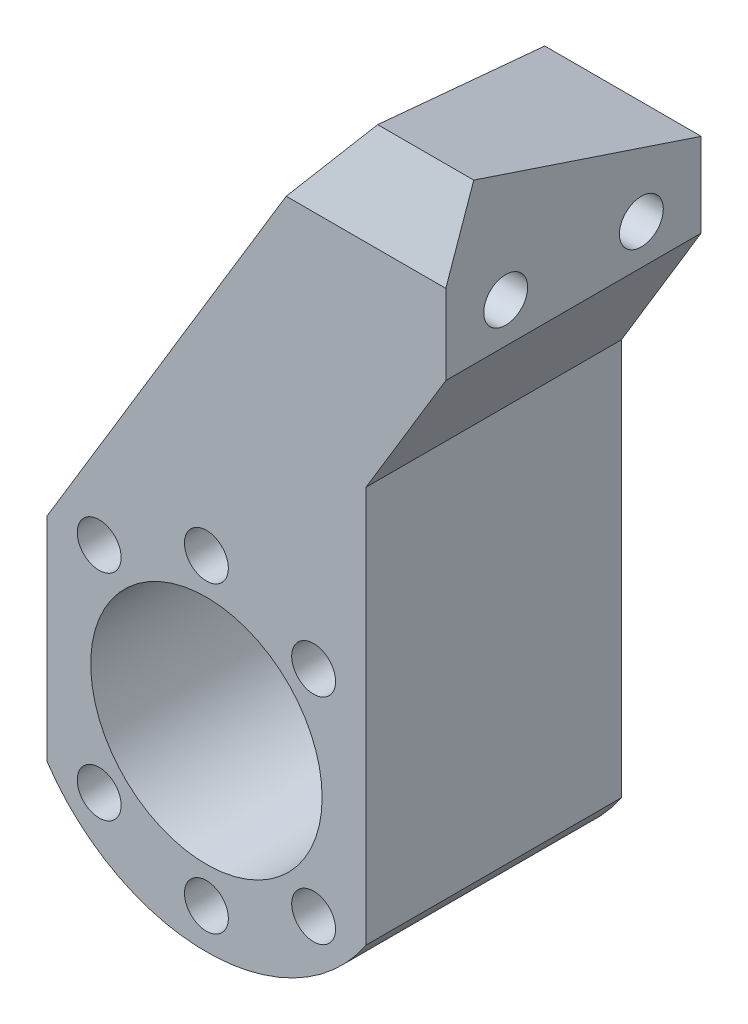
SolidWorks part; units mm, degrees
ref_plane "Plan de face" through (0, 0, 0) normal (0, 0, 1) x (1, 0, 0)
ref_plane "Plan de dessus" through (0, 0, 0) normal (0, 1, 0) x (1, 0, 0)
ref_plane "Plan de droite" through (0, 0, 0) normal (1, 0, 0) x (0, 0, -1)
sketch "Esquisse2" plane through (0, 0, 0) normal (0, 0, 1) x (1, 0, 0)
  line L0 (20, 13.2665) -> (20, -13.2665)
  line L1 (-20, 13.2665) -> (-20, -13.2665)
  line L2 (-20, 0) -> (20, 0) construction
  arc A2 (-20, 13.2665) -> (20, 13.2665) centre (0, 0) cw
  arc A3 (-20, -13.2665) -> (20, -13.2665) centre (0, 0) ccw
  circle A4 centre (0, 0) radius 19 construction
  circle A5 centre (0, 19) radius 2.75
  circle A6 centre (-13.435, 13.435) radius 2.75
  circle A7 centre (13.435, 13.435) radius 2.75
  circle A8 centre (0, -19) radius 2.75
  circle A9 centre (13.435, -13.435) radius 2.75
  circle A10 centre (-13.435, -13.435) radius 2.75
  circle A11 centre (0, 0) radius 14.5
  point P4 (0, 0)
  point P8 (0, 0)
  point P10 (-20, 0)
  point P11 (20, 0)
  dimension "D2" = 24
  dimension "D3" = 38
  dimension "D4" = 5.5
  dimension "D5" = 29
  dimension "D1" = 40
  dimension "D6" = 45
  dimension "D7" = 45
  dimension "D8" = 45
  dimension "D9" = 45
extrude "Boss.-Extru.1" add sketch "Esquisse2" along normal blind 32
sketch "Esquisse7" plane through (0, 0, 0) normal (0, 0, -1) x (-1, 0, 0)
  line L2 (-10, 63.001) -> (20, 13.2665)
  line L3 (-10, 63.001) -> (-30, 63.001)
  line L4 (-30, 63.001) -> (-30, 53.001)
  line L6 (-20, 13.2665) -> (-20, 36.4228)
  line L7 (-20, 36.4228) -> (-30, 53.001)
  arc A0 (20, 13.2665) -> (-20, 13.2665) centre (0, 0) ccw construction
  arc A1 (20, 13.2665) -> (-20, 13.2665) centre (0, 0) ccw
  dimension "D1" = 39.7345
  dimension "D2" = 10
  dimension "D3" = 10
  dimension "D4" = 20
extrude "Boss.-Extru.4" add sketch "Esquisse7" against normal up to surface (32 mm away) up to face at (0, 0, 32)
sketch "Esquisse10" plane through (30, 0, 0) normal (1, 0, 0) x (0, 0, -1)
  line L0 (-32, 53.001) -> (-32, 63.001) construction
  line L1 (-24.5, 58.001) -> (-7.5, 58.001) construction
  line L2 (-32, 63.001) -> (0, 63.001) construction
  circle A0 centre (-24.5, 58.001) radius 2.75
  circle A1 centre (-7.5, 58.001) radius 2.75
  point P4 (-16, 58.001)
  point P7 (-32, 58.001)
  point P10 (-16, 63.001)
  dimension "D1" = 5.5
  dimension "D2" = 7.5
extrude "Enlèv. mat.-Extru.3" cut sketch "Esquisse10" against normal up to next
sketch "Esquisse11" plane through (30, 0, 0) normal (1, 0, 0) x (0, 0, -1)
  line L0 (-32, 63.001) -> (0, 63.001)
  line L2 (-28.5, 73.001) -> (-32, 63.001)
  line L3 (0, 63.001) -> (0, 63.501)
  line L4 (0, 63.501) -> (-28.5, 73.001)
  dimension "D1" = 10
  dimension "D2" = 3.5
  dimension "D3" = 0.5
extrude "Boss.-Extru.6" add sketch "Esquisse11" against normal up to vertex (20 mm away) up to point (10, 63.001, 32)
sketch "Esquisse12" plane through (0, 0, 0) normal (0, 0, -1) x (-1, 0, 0)
  line L0 (-10, 63.001) -> (-17.9628, 73.001)
  line L2 (-10, 73.001) -> (-10, 63.001) construction
  line L3 (-10, 73.001) -> (-10, 63.001)
  line L5 (-10, 73.001) -> (-30, 73.001) construction
  line L6 (-17.9628, 73.001) -> (-10, 73.001)
extrude "Enlèv. mat.-Extru.4" cut sketch "Esquisse12" against normal up to next
ref_plane "Plan1" through (20, 0, 0) normal (1, 0, 0) x (0, 0, -1)
sketch "Esquisse13" plane through (20, 0, 0) normal (1, 0, 0) x (0, 0, -1)
  circle A0 centre (-7.5, 58.001) radius 6
  circle A1 centre (-24.5, 58.001) radius 6
  dimension "D1" = 12
extrude "Enlèv. mat.-Extru.5" cut sketch "Esquisse13" against normal up to next
